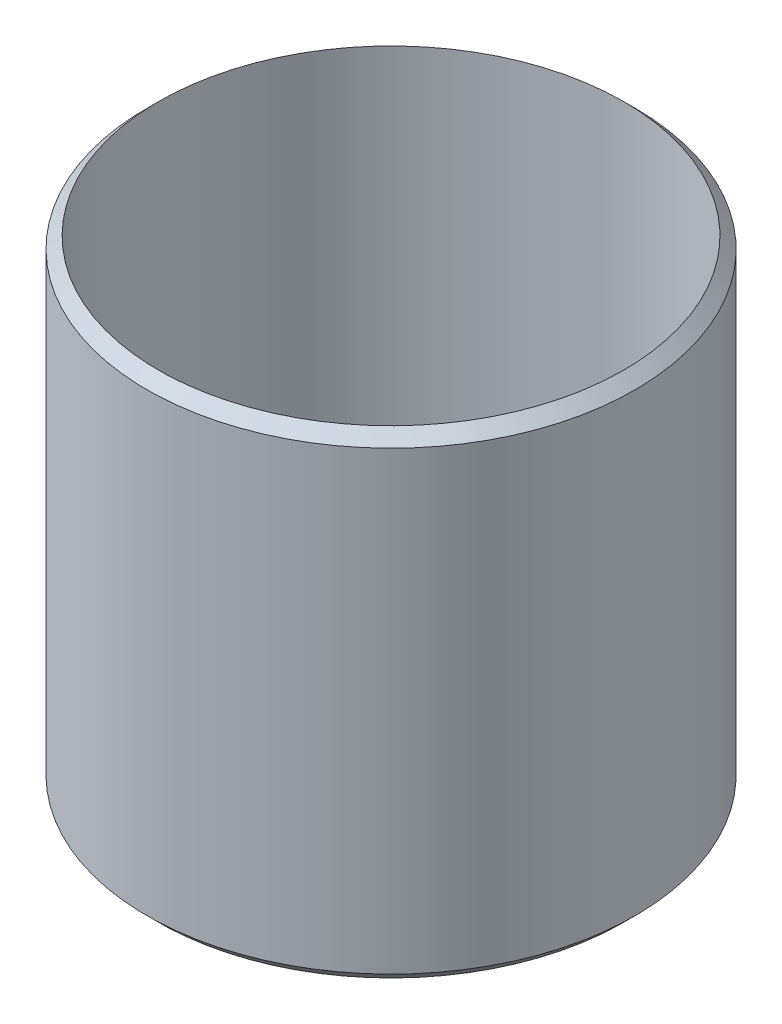
SolidWorks part; units mm, degrees
ref_plane "Front Plane" through (0, 0, 0) normal (0, 0, 1) x (1, 0, 0)
ref_plane "Top Plane" through (0, 0, 0) normal (0, 1, 0) x (1, 0, 0)
ref_plane "Right Plane" through (0, 0, 0) normal (1, 0, 0) x (0, 0, -1)
sketch "Sketch1" plane through (0, 0, 0) normal (0, 1, 0) x (1, 0, 0)
  circle A0 centre (0, 0) radius 36.322
  circle A1 centre (0, 0) radius 38.1
  dimension "D1" = 72.644
  dimension "D2" = 76.2
extrude "Boss-Extrude1" add sketch "Sketch1" along normal blind 76.2
chamfer "Chamfer1" distance 2.54 angle 45 2 edges at (0, 76.2, 38.1) (0, 0, 38.1)
